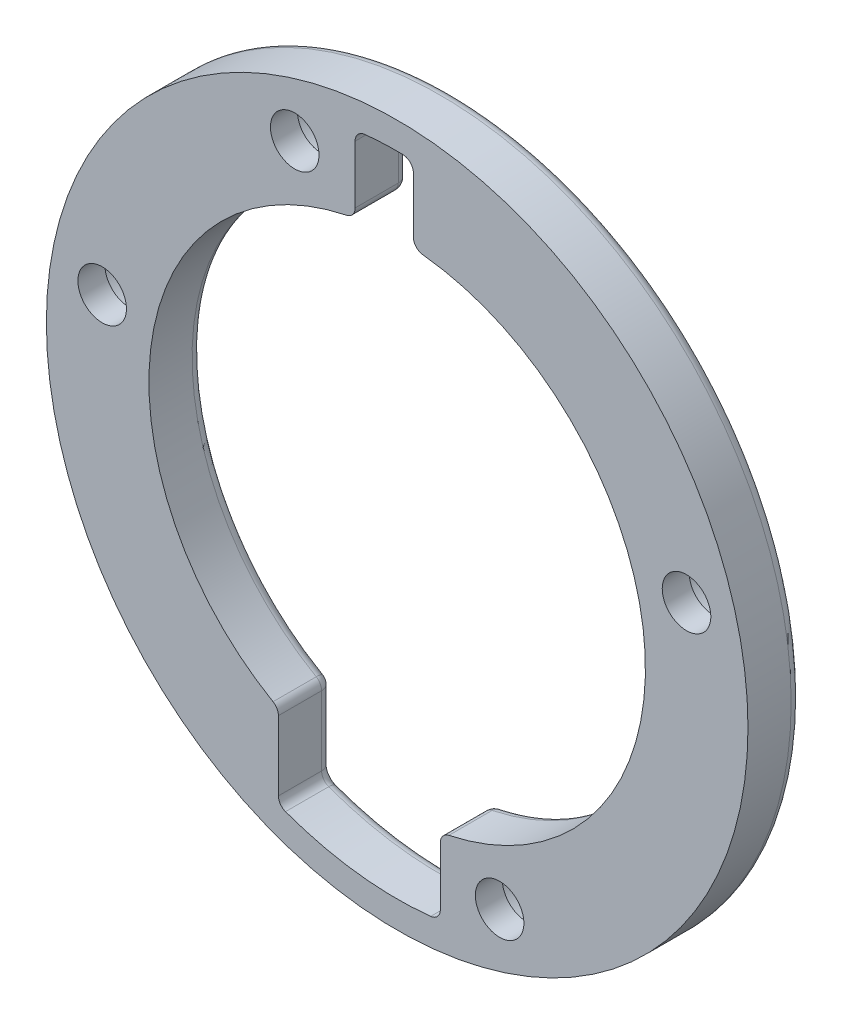
SolidWorks part; units mm, degrees
material "6061-T6 "
ref_plane "Plan de face" through (0, 0, 0) normal (0, 0, 1) x (1, 0, 0)
ref_plane "Plan de dessus" through (0, 0, 0) normal (0, 1, 0) x (1, 0, 0)
ref_plane "Plan de droite" through (0, 0, 0) normal (1, 0, 0) x (0, 0, -1)
sketch "Sketch1" plane through (0, 0, 0) normal (0, 0, 1) x (1, 0, 0)
  line L0 (-9.5, -22) -> (0, -22) construction
  line L1 (0, -22) -> (2.5, -22) construction
  line L3 (-2.5, -28) -> (-4.5, -28) construction
  line L5 (0, 22) -> (0, 27) construction
  line L7 (-9.5, -22) -> (-9.5, -23) construction
  line L9 (2.5, -22) -> (2.5, -23) construction
  line L11 (0, 22) -> (-2.4, 22) construction
  line L12 (-2.4, 22) -> (-2.4, 27) construction
  line L14 (-1.4, 28) -> (-1, 28) construction
  line L18 (4, -22.6495) -> (4, -29.7321)
  line L19 (0, 32.5) -> (0, -32.5) construction
  line L20 (-28.1458, -16.25) -> (28.1458, 16.25) construction
  line L21 (-22.9929, -0.5732) -> (-29.6713, -4.429)
  line L22 (-11, -20.199) -> (-11, -27.9106)
  line L23 (-3.9, 22.6669) -> (-3.9, 29.7454)
  line L24 (1.5, 22.951) -> (1.5, 29.9625)
  line L25 (20.6262, 10.1765) -> (26.6983, 13.6822)
  line L26 (0, 0) -> (26.8044, 7.1822) construction
  line L27 (-27.3284, 4.8187) -> (0, 0) construction
  line L28 (0, 0) -> (9.4911, -26.0765) construction
  line L29 (0, 0) -> (-9.4911, 26.0765) construction
  line L30 (-32.5, 0) -> (32.5, 0) construction
  circle A0 centre (0, 0) radius 28 construction
  circle A1 centre (0, 0) radius 30 construction
  circle A2 centre (0, 0) radius 32.5
  circle A3 centre (0, 0) radius 23
  arc A6 (-9.5, -23) -> (-4.5, -28) centre (-4.5, -23) ccw construction
  arc A7 (2.5, -23) -> (-2.5, -28) centre (-2.5, -23) cw construction
  arc A8 (-2.4, 27) -> (-1.4, 28) centre (-1.4, 27) cw construction
  arc A9 (0, 27) -> (-1, 28) centre (-1, 27) ccw construction
  arc A10 (-29.6713, -4.429) -> (4, -29.7321) centre (0, 0) ccw
  arc A11 (-3.9, 29.7454) -> (26.6983, 13.6822) centre (0, 0) cw
  circle A13 centre (-9.4911, 26.0765) radius 1.65 construction
  circle A14 centre (-27.3284, 4.8187) radius 1.65 construction
  circle A15 centre (9.4911, -26.0765) radius 1.65 construction
  circle A16 centre (26.8044, 7.1822) radius 1.65 construction
  circle A17 centre (0, 0) radius 27.75 construction
  dimension "D1" = 56
  dimension "D9" = 60
  dimension "D10" = 2.5
  dimension "D11" = 46
  dimension "D20" = 10
  dimension "D21" = 15
  dimension "D22" = 20
  dimension "D5" = 5
  dimension "D6" = 1
  dimension "D19" = 3.3
  dimension "D24" = 55.5
  dimension "D2" = 12
  dimension "D3" = 2.5
  dimension "D4" = 6
  dimension "D7" = 2.4
  dimension "D8" = 6
  dimension "D12" = 60
  dimension "D13" = 11
  dimension "D14" = 1.5
  dimension "D15" = 1.5
  dimension "D16" = 1.5
  dimension "D17" = 1.5
  dimension "D18" = 1.5
  dimension "D23" = 20
extrude "Boss-Extrude1" add sketch "Sketch1" against normal blind 5 contours A2 L23 A11 L25 A3 L18 A10 L21 | A11 L24 A3 L25 | L21 A10 L22 A3 region at (-20.6806, -14.8114, 0) region at (13.9466, 21.2914, 0) region at (-31.5808, 0, 0)
hole_wizard "CBORE for M4 SHCS1" positions "Sketch4" profile "Sketch3" counterbore size "M4" standard "ANSI Metric" end condition through all
sketch "Sketch4" plane through (0, 0, -5) normal (0, 0, -1) x (-1, 0, 0)
  point P0 (27.3284, 4.8187)
  point P3 (9.4911, 26.0765)
  point P6 (-26.8044, 7.1822)
  point P9 (-9.4911, -26.0765)
sketch "Sketch3" plane through (-27.3284, 4.8187, -5) normal (1, 0, 0) x (0, 1, 0)
  line L0 (0, 0) -> (0, 5)
  line L1 (0, 5) -> (2.25, 5)
  line L3 (2.25, 5) -> (2.25, 2.5)
  line L4 (2.25, 2.5) -> (4.25, 2.5)
  line L5 (4.25, 2.5) -> (4.25, 0)
  line L7 (4.25, 0) -> (0, 0)
  line L11 (0, -6.35) -> (0, 107.95) construction
  dimension "Thru Hole Dia." = 4.5
  dimension "Thru Hole Depth" = 5
  dimension "C'Bore Dia." = 8.5
  dimension "C'Bore Depth" = 2.5
fillet "Fillet2" radius 1 8 edges at (-11, -20.199, -2.5) (-11, -27.9106, -2.5) (4, -22.6495, -2.5) (4, -29.7321, -2.5) (1.5, 22.951, -2.5) (1.5, 29.9625, -2.5) (-3.9, 22.6669, -2.5) (-3.9, 29.7454, -2.5)
fillet "Fillet3" radius 1 17 edges at (-4.1241, 22.8637, -5) (-3.9, 26.1746, -5) (-3.6416, 29.5255, -5) (-1.2435, 29.9742, -5) (1.2132, 29.6967, -5) (1.5, 26.4326, -5) (1.757, 23.2002, -5) (22.968, 1.2129, -5) (4.2227, -22.8442, -5) (4, -26.1589, -5) (3.7428, -29.5139, -5) (-3.7167, -29.7689, -5) (-10.82, -27.7937, -5) (-11, -24.003, -5) (-11.134, -20.2846, -5) (-22.7099, 3.6415, -5) (32.5, 0, -5)
ref_axis "Axis1" through (9.4911, -26.0765, 0) along (0, 0, -1)
ref_axis "Axis2" through (-9.4911, 26.0765, 0) along (0, 0, -1)
ref_plane "Plane1" through (0, 0, 0) normal (-0.9397, -0.342, 0) x (0, 0, 1)
